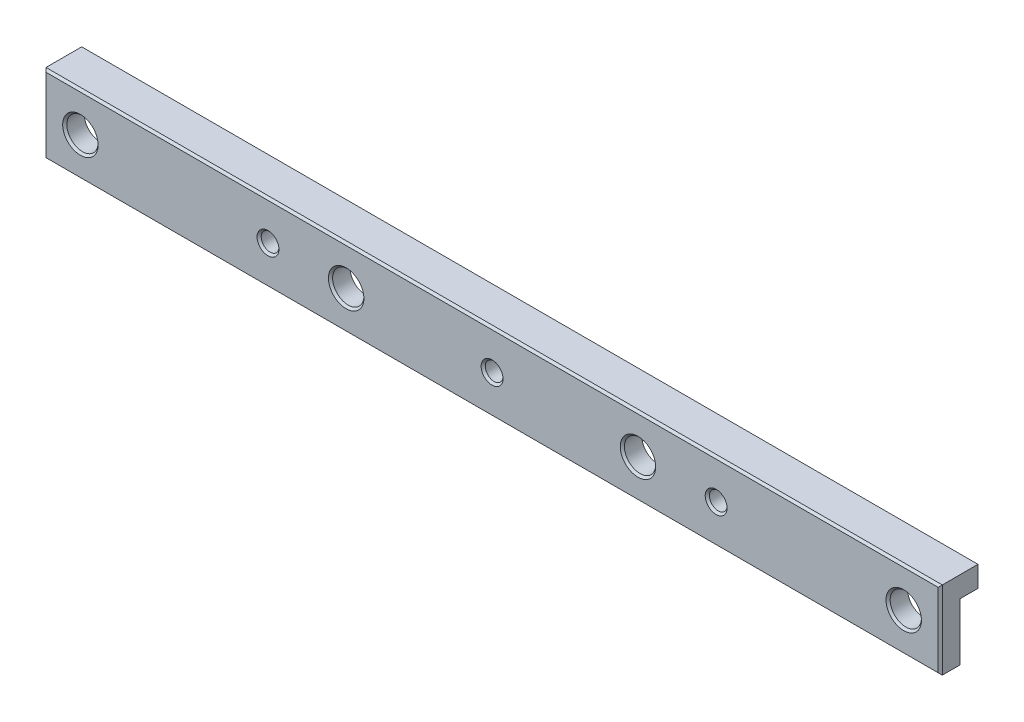
SolidWorks part; units mm, degrees
ref_plane "Front Plane" through (0, 0, 0) normal (0, 0, 1) x (1, 0, 0)
ref_plane "Top Plane" through (0, 0, 0) normal (0, 1, 0) x (1, 0, 0)
ref_plane "Right Plane" through (0, 0, 0) normal (1, 0, 0) x (0, 0, -1)
sketch "Sketch1" plane through (0, 0, 0) normal (0, 0, 1) x (1, 0, 0)
  line L0 (0, 7.5) -> (0, 0) construction
  line L1 (86, 7.5) -> (-86, 7.5)
  line L2 (86, 7.5) -> (86, 3.5)
  line L3 (86, -7.5) -> (-86, -7.5)
  line L4 (-86, 7.5) -> (-86, 3.5)
  line L5 (86, 3.5) -> (-86, 3.5)
  line L6 (-86, 3.5) -> (-86, -7.5)
  line L7 (86, 3.5) -> (86, -7.5)
  line L8 (0, 0) -> (0, -7.5) construction
  dimension "D1" = 172
  dimension "D2" = 7.5
  dimension "D3" = 4
extrude "Boss-Extrude1" add sketch "Sketch1" against normal blind 7.25 contours L7 L5 L6 L3 | L1 L0 L5 L2 | L0 L1 L4 L5 region at (0, 5.5, 0) region at (0, -2, 0)
extrude "Cut-Extrude1" cut sketch "Sketch1<6>" along normal blind 3.5 from surface contours L7 L5 L6 L3 region at (0, -2, 0) starting at face at (0, 0, -7.25)
sketch "Sketch1<6>" plane through (0, 0, 0) normal (0, 0, 1) x (1, 0, 0) same geometry as "Sketch1"
sketch "Sketch2" plane through (0, 0, 0) normal (0, 0, 1) x (1, 0, 0)
  line L0 (79, 0) -> (0, 0) construction
  line L1 (-86, 3.5) -> (-86, -7.5) construction
  line L2 (0, 0) -> (-79, 0) construction
  line L4 (-86, 0) -> (-43, 0) construction
  line L5 (-43, 0) -> (0, 0) construction
  line L6 (0, 0) -> (43, 0) construction
  line L7 (43, 0) -> (86, 0) construction
  circle A1 centre (-43, 0) radius 1.7
  circle A2 centre (0, 0) radius 1.7
  circle A3 centre (43, 0) radius 1.7
  circle A4 centre (-79, 0) radius 3
  circle A7 centre (79, 0) radius 3
  circle A10 centre (-28, 0) radius 3
  circle A11 centre (28, 0) radius 3
  dimension "D2" = 6
  dimension "D4" = 28
  dimension "D3" = 3.4
  dimension "D1" = 7
  dimension "D5" = 79
  dimension "D6" = 79
  dimension "D7" = 28
extrude "Cut-Extrude2" cut sketch "Sketch2" against normal through all both and the other way through all
chamfer "Chamfer1" distance 0.4 angle 45 11 edges at (0, -7.5, 0) (-86, 0, 0) (0, 7.5, 0) (86, 0, 0) (1.7, 0, 0) (31, 0, 0) (-25, 0, 0) (-41.3, 0, 0) (44.7, 0, 0) (-76, 0, 0) (82, 0, 0)
sketch "Sketch3" plane through (0, 0, 0) normal (0, 0, 1) x (1, 0, 0)
  line L2 (86, 3.5) -> (-86, 3.5) construction
  line L4 (0, 7.5) -> (0, 14.1762) construction
  line L5 (7.5035, -7.5) -> (7.5035, -14.1762) construction
  line L7 (7.6035, -7.5) -> (7.6035, -14.1762)
  line L8 (0.1, 7.5) -> (0.1, 14.1762)
  line L9 (7.4035, -7.5) -> (7.4035, -14.1762)
  line L10 (-0.1, 7.5) -> (-0.1, 14.1762)
  line L11 (86, 7.5) -> (-86, 7.5) construction
  line L12 (86, -7.5) -> (-86, -7.5) construction
  arc A0 (0, 7.5) -> (2.8723, 4.6277) centre (2.8723, 7.5) ccw construction
  arc A1 (2.1569, 2.6283) -> (2.8723, 4.6277) centre (2.8723, 3.5) ccw construction
  arc A2 (1.216, -3.1751) -> (7.5035, -7.5) centre (2.8723, -7.5) cw construction
  arc A3 (2.1569, 2.6283) -> (1.216, -3.1751) centre (0, 0) ccw construction
  arc A4 (1.1802, -3.0817) -> (7.6035, -7.5) centre (2.8723, -7.5) cw
  arc A5 (2.0935, 2.551) -> (1.1802, -3.0817) centre (0, 0) ccw
  arc A6 (2.0935, 2.551) -> (2.8723, 4.7277) centre (2.8723, 3.5) ccw
  arc A7 (0.1, 7.5) -> (2.8723, 4.7277) centre (2.8723, 7.5) ccw
  arc A8 (1.2517, -3.2685) -> (7.4035, -7.5) centre (2.8723, -7.5) cw
  arc A9 (2.2203, 2.7056) -> (1.2517, -3.2685) centre (0, 0) ccw
  arc A10 (2.2203, 2.7056) -> (2.8723, 4.5277) centre (2.8723, 3.5) ccw
  arc A11 (-0.1, 7.5) -> (2.8723, 4.5277) centre (2.8723, 7.5) ccw
  arc A12 (7.6035, -14.1762) -> (7.4035, -14.1762) centre (7.5035, -14.1762) cw
  arc A13 (0.1, 14.1762) -> (-0.1, 14.1762) centre (0, 14.1762) ccw
  arc A14 (2.1569, 2.6283) -> (1.216, -3.1751) centre (0, 0) ccw construction
  arc A15 (2.1569, 2.6283) -> (2.8723, 4.6277) centre (2.8723, 3.5) ccw construction
  dimension "D1" = 0.1
  dimension "D2" = 0.1
extrude "Cut-Extrude3" [suppressed] cut sketch "Sketch3" against normal through all both and the other way through all
